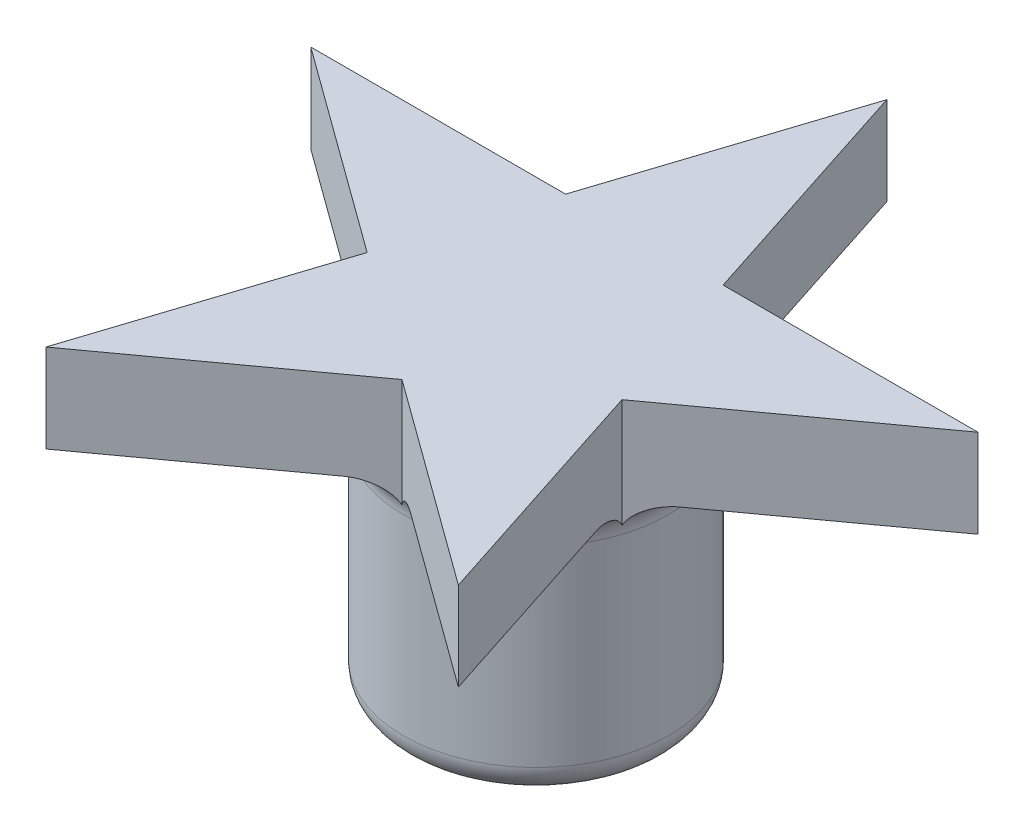
SolidWorks part; units mm, degrees
ref_plane "Front Plane" through (0, 0, 0) normal (0, 0, 1) x (1, 0, 0)
ref_plane "Top Plane" through (0, 0, 0) normal (0, 1, 0) x (1, 0, 0)
ref_plane "Right Plane" through (0, 0, 0) normal (1, 0, 0) x (0, 0, -1)
sketch "Sketch2" plane through (0, 0, 0) normal (0, 1, 0) x (1, 0, 0)
  circle A0 centre (0, 0) radius 4.5
  dimension "D1" = 9
extrude "Boss-Extrude1" add sketch "Sketch2" along normal blind 10
sketch "Sketch3" plane through (0, 10, 0) normal (0, 1, 0) x (1, 0, 0)
  line L0 (0, 11.9091) -> (-2.6738, 3.6801)
  line L6 (-11.3262, 3.6801) -> (-2.6738, 3.6801)
  line L7 (0, 11.9091) -> (2.6738, 3.6801)
  line L8 (11.3262, 3.6801) -> (4.3262, -1.4057)
  line L9 (-11.3262, 3.6801) -> (-4.3262, -1.4057)
  line L10 (0, -4.5489) -> (7, -9.6347)
  line L11 (-4.3262, -1.4057) -> (-7, -9.6347)
  line L12 (2.6738, 3.6801) -> (11.3262, 3.6801)
  line L13 (4.3262, -1.4057) -> (7, -9.6347)
  line L14 (0, -4.5489) -> (-7, -9.6347)
  dimension "D1" = 14
sketch "Sketch4" plane through (0, 0, 0) normal (0, -1, 0) x (1, 0, 0)
  circle A0 centre (0, 0) radius 1.25
  dimension "D1" = 2.5
extrude "Cut-Extrude1" cut sketch "Sketch4" against normal blind 2.5
sketch "Sketch5" plane through (0, 2.5, 0) normal (0, -1, 0) x (1, 0, 0)
  line L2 (-0.75, 1) -> (-0.75, -1)
  line L4 (0.75, 1) -> (0.75, -1)
  arc A0 (-0.75, -1) -> (0.75, -1) centre (0, 0) ccw
  arc A1 (0.75, 1) -> (-0.75, 1) centre (0, 0) ccw
  point P0 (0, 0)
  dimension "D2" = 2.5
extrude "Cut-Extrude4" cut sketch "Sketch5" against normal blind 6 contours L2 A0 L4 A1
extrude "Boss-Extrude7" add sketch "Sketch3" along normal blind 1.5 and the other way blind 1.5 contours L6 L0 L7 L12 L8 L13 L10 L14 L11 L9
fillet "Fillet2" radius 1 2 edges at (0, 0, 4.5) (0, 8.5, -4.5)
